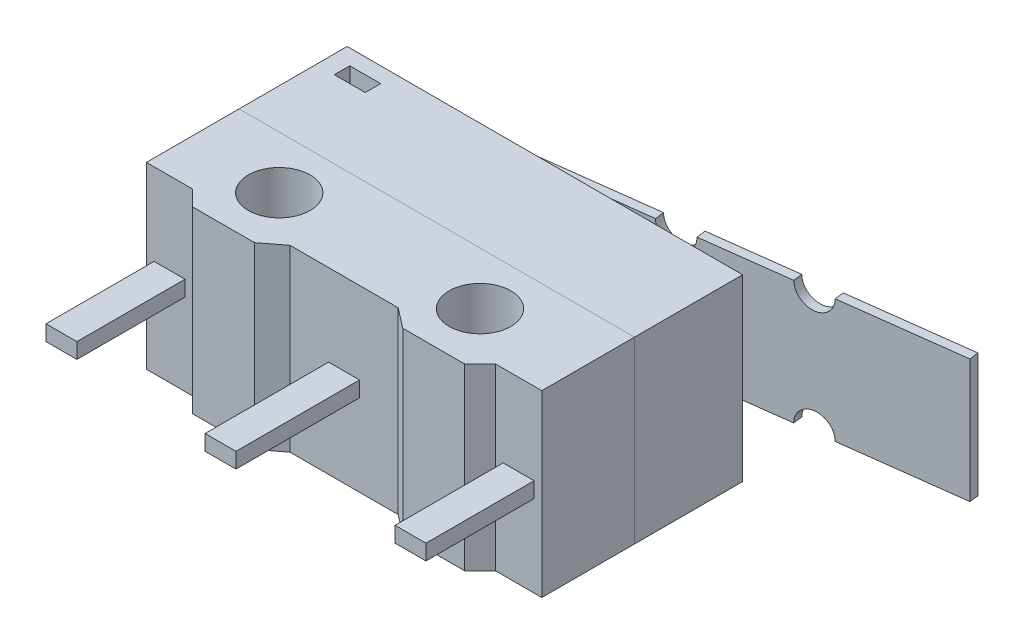
SolidWorks part; units mm, degrees
ref_plane "Front" through (0, 0, 0) normal (0, 0, 1) x (1, 0, 0)
ref_plane "Top" through (0, 0, 0) normal (0, 1, 0) x (1, 0, 0)
ref_plane "Right" through (0, 0, 0) normal (1, 0, 0) x (0, 0, -1)
sketch "Эскиз1" plane through (0, 0, 0) normal (0, 0, 1) x (1, 0, 0)
  line L1 (-6.4, -2.9) -> (6.4, -2.9)
  line L2 (-6.4, -2.9) -> (-6.4, 2.9)
  line L3 (-6.4, 2.9) -> (6.4, 2.9)
  line L4 (6.4, -2.9) -> (6.4, 2.9)
  line L5 (-6.4, 0) -> (6.4, 0) construction
  dimension "D1" = 12.8
  dimension "D2" = 5.8
extrude "Вытянуть1" add sketch "Эскиз1" along normal blind 3.5
sketch "Эскиз2" plane through (0, 0, 0) normal (0, 0, -1) x (-1, 0, 0)
  line L0 (-6.4, -2.9) -> (-6.4, 2.9) construction
  line L1 (-2.9, -1.45) -> (-1.9, -1.45)
  line L2 (-2.9, -1.45) -> (-2.9, 1.45)
  line L3 (-2.9, 1.45) -> (-1.9, 1.45)
  line L4 (-1.9, -1.45) -> (-1.9, 1.45)
  line L5 (-2.9, 0) -> (-6.4, 0) construction
  dimension "D1" = 1
  dimension "D2" = 2.9
  dimension "D3" = 3.5
extrude "Вытянуть2" add sketch "Эскиз2" along normal blind 1.05
fillet "Скругление1" radius 0.5 2 edges at (2.9, 0, -1.05) (1.9, 0, -1.05)
sketch "Эскиз3" plane through (0, 0, 0) normal (0, 0, -1) x (-1, 0, 0)
  line L0 (5.8156, 0) -> (6.4, 0) construction
  line L1 (4.8156, 2) -> (5.8156, 2)
  line L2 (4.8156, 2) -> (4.8156, -2)
  line L3 (4.8156, -2) -> (5.8156, -2)
  line L4 (5.8156, 2) -> (5.8156, -2)
  line L5 (6.4, 2.9) -> (6.4, -2.9) construction
  dimension "D1" = 1
  dimension "D2" = 4
  dimension "D3" = 0.5844
extrude "Вырез-Вытянуть1" cut sketch "Эскиз3" against normal blind 1
sketch "Эскиз4" plane through (0, -2.9, 0) normal (0, -1, 0) x (1, 0, 0)
  line L0 (-4.8156, 1) -> (-4.8156, 0) construction
  line L1 (-4.8156, 0.5) -> (-5.8156, 0.5)
  line L2 (-4.8156, 0.5) -> (-4.8156, 1)
  line L3 (-4.8156, 1) -> (-5.8156, 1)
  line L4 (-5.8156, 0.5) -> (-5.8156, 1)
  line L5 (-5.8156, 1) -> (-5.8156, 0) construction
  line L6 (-4.8156, 1) -> (-5.8156, 1) construction
extrude "Вырез-Вытянуть2" cut sketch "Эскиз4" against normal through all
extrude "Вытянуть110" add sketch "Эскиз110" along normal blind 5.8 separate body
sketch "Эскиз110" plane through (1.5925, 2.9, -4.7605) normal (0, -1, 0) x (1, 0, 0)
  line L0 (-7.9925, 8.2605) -> (4.8075, 8.2605)
  line L1 (4.8075, 8.2605) -> (4.8075, 11.2605)
  line L2 (4.8075, 11.2605) -> (3.3075, 11.2605)
  line L3 (-7.9925, 8.2605) -> (-7.9925, 11.2605)
  line L4 (-1.5925, -3.6435) -> (-1.5925, 11.039) construction
  line L5 (-3.3425, 11.2605) -> (0.1575, 11.2605)
  line L6 (-7.9925, 11.2605) -> (-6.4925, 11.2605)
  line L7 (-5.9925, 11.7605) -> (-3.9925, 11.7605)
  line L8 (-7.9925, 8.2605) -> (4.8075, 8.2605) construction
  line L9 (-6.4925, 11.2605) -> (-5.9925, 11.7605)
  line L10 (-3.9925, 11.7605) -> (-3.3425, 11.2605)
  line L11 (3.3075, 11.2605) -> (2.8075, 11.7605)
  line L12 (2.8075, 11.7605) -> (0.8075, 11.7605)
  line L13 (0.8075, 11.7605) -> (0.1575, 11.2605)
  dimension "D1" = 135
  dimension "D2" = 3
  dimension "D3" = 12.8
  dimension "D4" = 1.5
  dimension "D5" = 3.5
  dimension "D7" = 2
  dimension "D8" = 3.5
sketch "Эскиз6" plane through (-1.5925, 3.5, 6.5) normal (0, 0, 1) x (1, 0, 0)
  line L1 (1.0925, -3.25) -> (2.0925, -3.25)
  line L2 (1.0925, -3.25) -> (1.0925, -3.75)
  line L3 (1.0925, -3.75) -> (2.0925, -3.75)
  line L4 (2.0925, -3.25) -> (2.0925, -3.75)
  line L6 (-4.8075, -3.5) -> (1.0925, -3.5) construction
  line L9 (-4.8075, -6.4) -> (-4.8075, -0.6) construction
  line L10 (1.5925, -3.25) -> (1.5925, -0.6) construction
  line L11 (3.3425, -0.6) -> (-0.1575, -0.6) construction
  dimension "D1" = 1
  dimension "D2" = 0.5
sketch "Эскиз7" plane through (1.5925, 2.9, -2.4605) normal (0, 1, 0) x (-1, 0, 0)
  line L0 (7.9925, 5.9605) -> (-4.8075, 5.9605) construction
  line L1 (-4.8075, 5.9605) -> (-4.8075, 8.9605) construction
  circle A0 centre (-1.5075, 7.6605) radius 1
  circle A1 centre (4.9925, 7.6605) radius 1
  dimension "D1" = 2
  dimension "D4" = 6.5
  dimension "D2" = 1.7
  dimension "D3" = 3.3
extrude "Вытянуть3" add sketch "Эскиз6" along normal blind 4
sketch "Эскиз5" plane through (-1.5925, 3.5, 6.5) normal (0, 0, 1) x (1, 0, 0)
  line L0 (7.2425, -0.6) -> (7.2425, -3.5) construction
  line L1 (-4.5575, -3.25) -> (-3.5575, -3.25)
  line L2 (-4.5575, -3.25) -> (-4.5575, -3.75)
  line L3 (-4.5575, -3.75) -> (-3.5575, -3.75)
  line L4 (-3.5575, -3.25) -> (-3.5575, -3.75)
  line L6 (-4.8075, -3.5) -> (-4.5575, -3.5) construction
  line L7 (-4.8075, -6.4) -> (-4.8075, -0.6) construction
  line L9 (-4.0575, -0.6) -> (-4.0575, -3.5) construction
  line L10 (-3.3075, -0.6) -> (-4.8075, -0.6) construction
  line L11 (7.9925, -0.6) -> (6.4925, -0.6) construction
  line L15 (6.7425, -3.25) -> (7.7425, -3.25)
  line L16 (6.7425, -3.25) -> (6.7425, -3.75)
  line L17 (6.7425, -3.75) -> (7.7425, -3.75)
  line L18 (7.7425, -3.25) -> (7.7425, -3.75)
  point P4 (-4.0575, -3.25)
  point P13 (7.2425, -3.25)
  dimension "D1" = 1
  dimension "D2" = 0.5
extrude "Вытянуть210" add sketch "Эскиз5" along normal blind 3.5
extrude "Вырез-Вытянуть110" cut sketch "Эскиз7" against normal through all
ref_plane "Плоскость1" through (-0.0935, 0, -0.7313) normal (-0.1268, 0, -0.9919) x (-0.9919, 0, 0.1268)
sketch "Эскиз111" plane through (-0.0935, 0, -0.7313) normal (-0.1268, 0, -0.9919) x (-0.9919, 0, 0.1268)
  line L0 (5.7687, -0.5) -> (-2.2313, -0.5)
  line L1 (5.7687, -2) -> (5.7687, -0.5)
  line L2 (5.7687, -2) -> (-2.6313, -2)
  line L3 (-11.7313, -2) -> (-11.7313, 2)
  line L4 (5.7687, 2) -> (-2.6313, 2)
  line L5 (-2.2313, -0.5) -> (-2.2313, 0.5)
  line L6 (-2.2313, 0.5) -> (5.7687, 0.5)
  line L7 (5.7687, 0.5) -> (5.7687, 2)
  line L8 (-11.7313, 0) -> (5.7687, 0) construction
  line L10 (-7.8313, -2) -> (-11.7313, -2)
  line L11 (-3.8313, -2) -> (-6.6313, -2)
  line L12 (-7.8313, 2) -> (-11.7313, 2)
  line L13 (-3.8313, 2) -> (-6.6313, 2)
  line L14 (5.7687, -2) -> (5.7687, 2) construction
  arc A0 (-3.8313, -2) -> (-2.6313, -2) centre (-3.2313, -2) cw
  arc A1 (-3.8313, 2) -> (-2.6313, 2) centre (-3.2313, 2) ccw
  arc A2 (-7.8313, -2) -> (-6.6313, -2) centre (-7.2313, -2) cw
  arc A3 (-7.8313, 2) -> (-6.6313, 2) centre (-7.2313, 2) ccw
  dimension "D5" = 9
  dimension "D6" = 4
  dimension "D7" = 0.6
  dimension "D1" = 17.5
  dimension "D2" = 4
  dimension "D3" = 1
  dimension "D4" = 8
extrude "Вытянуть212" add sketch "Эскиз111" along normal blind 0.3 separate body
